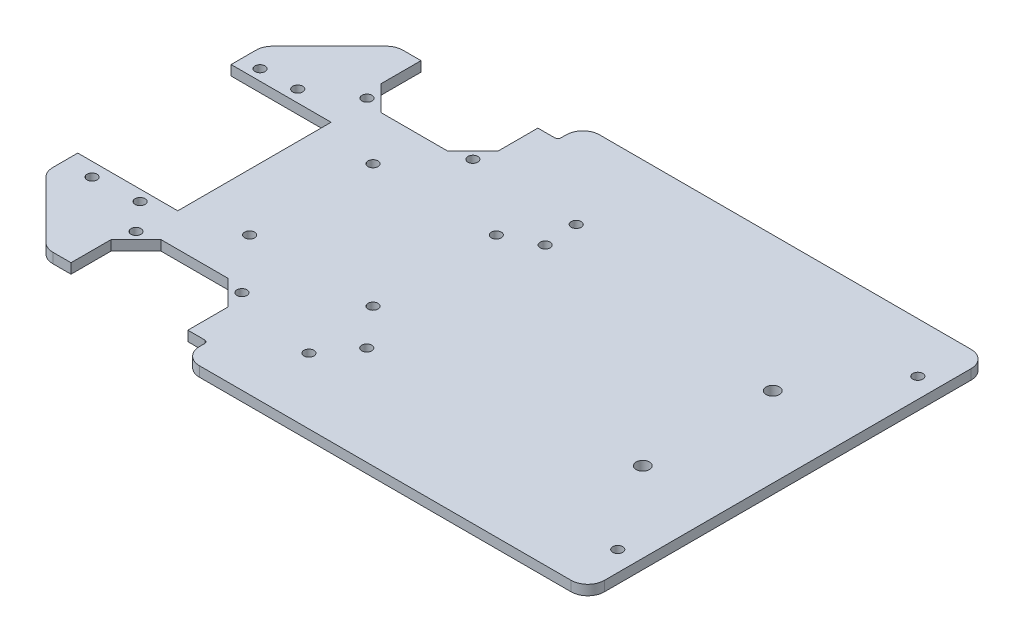
SolidWorks part; units mm, degrees
ref_plane "Front Plane" through (0, 0, 0) normal (0, 0, 1) x (1, 0, 0)
ref_plane "Top Plane" through (0, 0, 0) normal (0, 1, 0) x (1, 0, 0)
ref_plane "Right Plane" through (0, 0, 0) normal (1, 0, 0) x (0, 0, -1)
sketch "Sketch1" plane through (0, 0, 0) normal (0, 1, 0) x (1, 0, 0)
  line L0 (190, 0) -> (0, 0) construction
  line L1 (0, -60) -> (190, -60)
  line L2 (0, -60) -> (0, 60)
  line L3 (0, 60) -> (190, 60)
  line L4 (190, -60) -> (190, 60)
  line L5 (0, -32.5266) -> (27.4734, -60)
  line L6 (30, 23) -> (0, 23) construction
  line L7 (30, 23) -> (30, -23) construction
  line L8 (30, -23) -> (0, -23) construction
  line L9 (0, 23) -> (0, -23)
  line L10 (30, 23) -> (0, -23) construction
  line L11 (30, -23) -> (0, 23) construction
  line L12 (19.9734, -52.5) -> (27.4734, -52.5) construction
  line L13 (68.5266, -52.5) -> (68.5266, -60) construction
  line L14 (35, -33) -> (27.4734, -40.5266) construction
  line L15 (27.4734, -52.5) -> (27.4734, -40.5266) construction
  line L16 (27.4734, -40.5266) -> (27.4734, -52.5) construction
  line L17 (0, 32.5266) -> (27.4734, 60)
  line L18 (35, -33) -> (55, -33) construction
  line L19 (55, -33) -> (62.5266, -40.5266) construction
  line L20 (62.5266, -52.5) -> (68.5266, -52.5) construction
  line L21 (47.5, -37) -> (42.5, -37) construction
  line L22 (45, -37) -> (45, -33) construction
  line L23 (45, -56.5) -> (45, -52.5) construction
  line L24 (39.4, -56.5) -> (50.6, -56.5) construction
  line L25 (27.4734, -52.5) -> (62.5266, -52.5) construction
  line L27 (62.5266, -40.5266) -> (62.5266, -52.5) construction
  point P7 (0, 0)
  point P8 (15, 0)
  dimension "D1" = 120
  dimension "D2" = 190
  dimension "D3" = 30
  dimension "D4" = 23
  dimension "D5" = 10
  dimension "D6" = 20
  dimension "D7" = 45
  dimension "D8" = 45
  dimension "D9" = 45
  dimension "D10" = 7.5
  dimension "D11" = 6
extrude "Boss-Extrude1" add sketch "Sketch1" along normal blind 3 contours L7 L8 L2 L1 L4 L3 L6 region at (97.9391, 0, 0)
sketch "Sketch4" plane through (0, 0, 0) normal (0, 1, 0) x (1, 0, 0)
  line L0 (68.5266, -60) -> (68.5266, -52.5)
  line L1 (68.5266, -52.5) -> (62.5266, -52.5)
  line L2 (62.5266, -52.5) -> (62.5266, -40.5266)
  line L3 (62.5266, -40.5266) -> (55, -33)
  line L4 (55, -33) -> (35, -33)
  line L5 (35, -33) -> (27.4734, -40.5266)
  line L6 (27.4734, -40.5266) -> (27.4734, -52.5)
  line L7 (27.4734, -52.5) -> (19.9734, -52.5)
  line L8 (19.9734, -52.5) -> (27.4734, -60)
  line L9 (27.4734, -60) -> (68.5266, -60)
  line L10 (0, 0) -> (190, 0) construction
  line L11 (190, -60) -> (190, 60) construction
  line L12 (27.4734, 60) -> (68.5266, 60)
  line L13 (19.9734, 52.5) -> (27.4734, 60)
  line L14 (27.4734, 52.5) -> (19.9734, 52.5)
  line L15 (27.4734, 40.5266) -> (27.4734, 52.5)
  line L16 (35, 33) -> (27.4734, 40.5266)
  line L17 (55, 33) -> (35, 33)
  line L18 (62.5266, 40.5266) -> (55, 33)
  line L19 (62.5266, 52.5) -> (62.5266, 40.5266)
  line L20 (68.5266, 52.5) -> (62.5266, 52.5)
  line L21 (68.5266, 60) -> (68.5266, 52.5)
  line L23 (30, 23) -> (0, 23)
  line L24 (30, 23) -> (30, -23)
  line L25 (30, -23) -> (0, -23)
  line L26 (0, 23) -> (0, -23)
extrude "Cut-Extrude1" cut sketch "Sketch4" along normal up to surface (3 mm away) up to face at (72.4911, 3, 0)
fillet "Fillet1" radius 5 8 edges at (19.9734, 1.5, -52.5) (0, 1.5, -32.5266) (68.5266, 1.5, -60) (190, 1.5, -60) (190, 1.5, 60) (0, 1.5, 32.5266) (19.9734, 1.5, 52.5) (68.5266, 1.5, 60)
fillet "Fillet2" radius 1 2 edges at (68.5266, 1.5, -52.5) (68.5266, 1.5, 52.5)
sketch "Sketch5" plane through (0, 0, 0) normal (0, 1, 0) x (1, 0, 0)
  circle A0 centre (47.0626, -18.5) radius 1.5 construction
  circle A1 centre (47.0626, -18.5) radius 1.5
  circle A2 centre (84.0626, -18.5) radius 1.5 construction
  circle A3 centre (84.0626, -18.5) radius 1.5
  circle A4 centre (84.0626, 18.5) radius 1.5 construction
  circle A5 centre (84.0626, 18.5) radius 1.5
  circle A6 centre (47.0626, 18.5) radius 1.5 construction
  circle A7 centre (47.0626, 18.5) radius 1.5
  circle A8 centre (94, 23.2195) radius 1.5 construction
  circle A9 centre (94, 23.2195) radius 1.5
  circle A10 centre (93.3054, 33.2195) radius 1.5 construction
  circle A11 centre (93.3054, 33.2195) radius 1.5
  circle A12 centre (29.1154, 34.642) radius 1.5 construction
  circle A13 centre (60.8846, 34.642) radius 1.5 construction
  circle A14 centre (8.3674, -27.0854) radius 1.5 construction
  circle A15 centre (16.3794, 26.6064) radius 1.5 construction
  circle A16 centre (94, -30.308) radius 1.5 construction
  circle A17 centre (86.6598, -40.308) radius 1.5 construction
  circle A18 centre (29.1154, 34.642) radius 1.5
  circle A19 centre (60.8846, 34.642) radius 1.5
  circle A20 centre (8.3674, -27.0854) radius 1.5
  circle A21 centre (16.3794, 26.6064) radius 1.5
  circle A22 centre (94, -30.308) radius 1.5
  circle A23 centre (86.6598, -40.308) radius 1.5
  circle A24 centre (184, -45) radius 1.5 construction
  circle A25 centre (184, 45) radius 1.5 construction
  circle A26 centre (184, -45) radius 1.5
  circle A27 centre (184, 45) radius 1.5
  circle A28 centre (166, -19.5) radius 2 construction
  circle A29 centre (166, 19.5) radius 2 construction
  circle A30 centre (166, -19.5) radius 2
  circle A31 centre (166, 19.5) radius 2
  circle A32 centre (29.1154, -34.642) radius 1.5 construction
  circle A33 centre (60.8846, -34.642) radius 1.5 construction
  circle A34 centre (29.1154, -34.642) radius 1.5
  circle A35 centre (60.8846, -34.642) radius 1.5
  circle A36 centre (21.9337, -26.25) radius 1.5 construction
  circle A37 centre (5.4397, 26.25) radius 1.5 construction
  circle A38 centre (21.9337, -26.25) radius 1.5
  circle A39 centre (5.4397, 26.25) radius 1.5
extrude "Cut-Extrude2" cut sketch "Sketch5" along normal up to surface (3 mm away) up to face at (55.2686, 3, 0)
